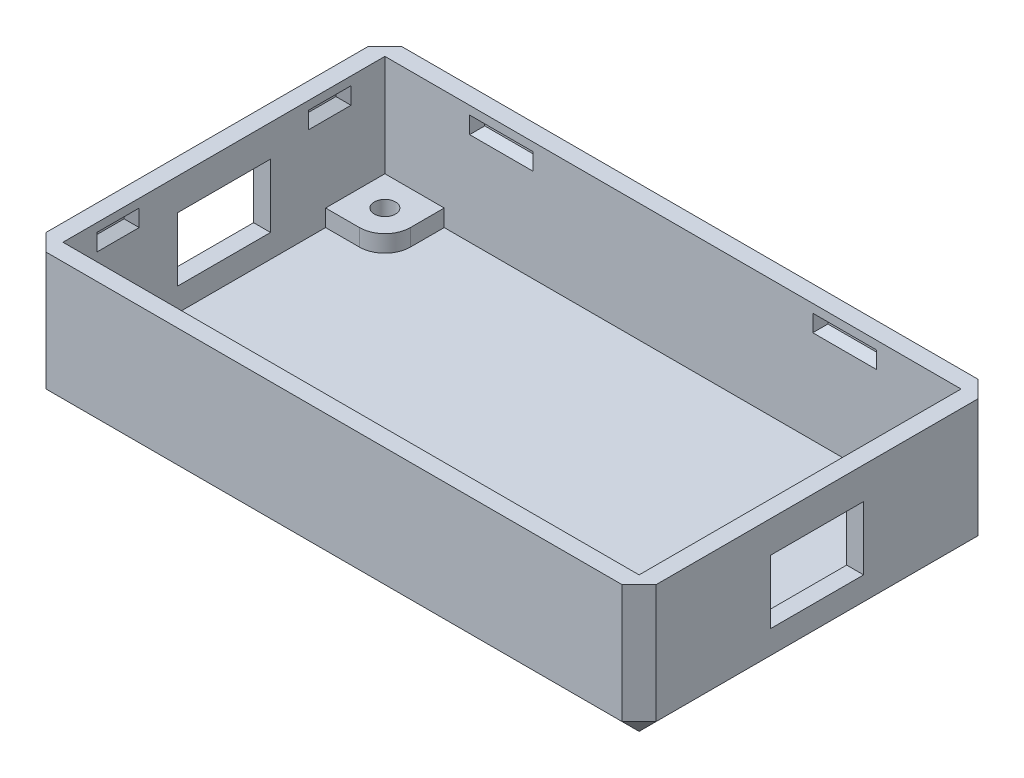
SolidWorks part; units mm, degrees
ref_plane "Front" through (0, 0, 0) normal (0, 0, 1) x (1, 0, 0)
ref_plane "Top" through (0, 0, 0) normal (0, 1, 0) x (1, 0, 0)
ref_plane "Right" through (0, 0, 0) normal (1, 0, 0) x (0, 0, -1)
sketch "Sketch1" plane through (0, 0, 0) normal (0, 1, 0) x (1, 0, 0)
  line L0 (-36, 21) -> (36, 21)
  line L1 (-34, -19) -> (34, -19)
  line L2 (-34, -19) -> (-34, 19)
  line L3 (-34, 19) -> (34, 19)
  line L4 (34, -19) -> (34, 19)
  line L5 (-34, -19) -> (34, 19) construction
  line L6 (-34, 19) -> (34, -19) construction
  line L7 (36, -21) -> (36, 21)
  line L8 (-36, -21) -> (36, -21)
  line L9 (-36, -21) -> (-36, 21)
  point P0 (0, 0)
  dimension "D1" = 38
  dimension "D2" = 68
  dimension "D3" = 2
extrude "Boss-Extrude1" add sketch "Sketch1" along normal blind 2 contours L1 L4 L3 L2 | L9 L8 L7 L0 L4 L1 L2 L3 region at (0, 0, -20.1665) region at (0, 0, 0)
extrude "Boss-Extrude2" add sketch "Sketch1<3>" along normal blind 14 from surface starting at face at (0, 2, 0)
sketch "Sketch1<3>" plane through (0, 0, 0) normal (0, 1, 0) x (1, 0, 0) same geometry as "Sketch1"
chamfer "Chamfer1" distance 2 angle 45 8 edges at (0, 0, 21) (36, 8, 21) (36, 0, 0) (36, 8, -21) (0, 0, -21) (-36, 8, -21) (-36, 0, 0) (-36, 8, 21)
sketch "Sketch2" plane through (0, 2, 0) normal (0, 1, 0) x (1, 0, 0)
  line L0 (-34, 12) -> (-30, 12)
  line L1 (-34, 19) -> (-27, 19)
  line L2 (-34, 19) -> (-34, 12)
  line L3 (-34, 12) -> (-27, 12) construction
  line L4 (-27, 19) -> (-27, 12) construction
  line L5 (-27, 19) -> (-27, 15)
  line L7 (-30.5, -15.5) -> (30.5, -15.5) construction
  line L8 (-30.5, -15.5) -> (-30.5, 15.5) construction
  line L9 (-30.5, 15.5) -> (30.5, 15.5) construction
  line L10 (30.5, -15.5) -> (30.5, 15.5) construction
  line L11 (-30.5, -15.5) -> (30.5, 15.5) construction
  line L12 (-30.5, 15.5) -> (30.5, -15.5) construction
  circle A0 centre (-30.5, 15.5) radius 1.25
  arc A1 (-30, 12) -> (-27, 15) centre (-30, 15) ccw
  point P7 (0, 0)
  point P8 (-27, 15.5)
  point P10 (-30.5, 12)
  point P13 (-27, 12)
  dimension "D1" = 3
  dimension "D3" = 2.5
  dimension "D2" = 31
extrude "Boss-Extrude3" add sketch "Sketch2" along normal blind 2
mirror "Mirror1" about plane through (0, 0, 0) normal (0, 0, 1) of "Boss-Extrude3"
mirror "Mirror2" about plane through (0, 0, 0) normal (1, 0, 0) of "Boss-Extrude3", "Mirror1"
sketch "Sketch3" plane through (0, 0, 0) normal (0, -1, 0) x (1, 0, 0)
  line L0 (-31.799, 17.75) -> (-29.201, 17.75)
  line L1 (-29.201, 17.75) -> (-27.9019, 15.5)
  line L2 (-27.9019, 15.5) -> (-29.201, 13.25)
  line L3 (-29.201, 13.25) -> (-31.799, 13.25)
  line L4 (-31.799, 13.25) -> (-33.0981, 15.5)
  line L5 (-33.0981, 15.5) -> (-31.799, 17.75)
  circle A1 centre (-30.5, 15.5) radius 2.5981 construction
  dimension "D1" = 4.5
extrude "Cut-Extrude1" cut sketch "Sketch3" against normal blind 1.6
mirror "Mirror3" about plane through (0, 0, 0) normal (0, 0, 1) of "Cut-Extrude1"
mirror "Mirror4" about plane through (0, 0, 0) normal (1, 0, 0) of "Mirror3", "Cut-Extrude1"
sketch "Sketch4" plane through (0, 2, 0) normal (0, 1, 0) x (1, 0, 0)
  circle A0 centre (30.5, -15.5) radius 1.25
  circle A1 centre (30.5, 15.5) radius 1.25
  circle A2 centre (-30.5, 15.5) radius 1.25
  circle A3 centre (-30.5, -15.5) radius 1.25
  circle A4 centre (-30.5, -15.5) radius 1.25 construction
extrude "Cut-Extrude2" cut sketch "Sketch4" against normal through all both and the other way through all
sketch "Sketch5" plane through (0, 0, 19) normal (0, 0, -1) x (-1, 0, 0)
  line L0 (34, 16) -> (-34, 16) construction
  line L1 (-24, 15) -> (-16.5, 15)
  line L2 (-24, 15) -> (-24, 13)
  line L3 (-24, 13) -> (-16.5, 13)
  line L4 (-16.5, 15) -> (-16.5, 13)
  line L5 (-34, 16) -> (-34, 2) construction
  dimension "D1" = 2
  dimension "D2" = 1
  dimension "D3" = 7.5
  dimension "D4" = 10
extrude "Cut-Extrude3" cut sketch "Sketch5" against normal blind 1 draft 38
mirror "Mirror5" about plane through (0, 0, 0) normal (0, 0, 1) of "Cut-Extrude3"
mirror "Mirror8" about plane through (0, 0, 0) normal (1, 0, 0) of "Mirror5", "Cut-Extrude3"
sketch "Sketch6" plane through (-34, 0, 0) normal (1, 0, 0) x (0, 0, -1)
  line L0 (19, 16) -> (-19, 16) construction
  line L1 (-15, 15) -> (-10, 15)
  line L2 (-15, 15) -> (-15, 13)
  line L3 (-15, 13) -> (-10, 13)
  line L4 (-10, 15) -> (-10, 13)
  dimension "D1" = 2
  dimension "D2" = 5
  dimension "D3" = 1
  dimension "D4" = 10
extrude "Cut-Extrude4" cut sketch "Sketch6" against normal blind 1 draft 38
mirror "Mirror6" about plane through (0, 0, 0) normal (1, 0, 0) of "Cut-Extrude4"
mirror "Mirror7" about plane through (0, 0, 0) normal (0, 0, 1) of "Mirror6", "Cut-Extrude4"
sketch "Sketch7" plane through (36, 0, 0) normal (1, 0, 0) x (0, 0, -1)
  line L1 (-5.5, 12.25) -> (5.5, 12.25)
  line L2 (-5.5, 12.25) -> (-5.5, 4.75)
  line L3 (-5.5, 4.75) -> (5.5, 4.75)
  line L4 (5.5, 12.25) -> (5.5, 4.75)
  point P4 (0, 4.75)
  dimension "D1" = 11
  dimension "D2" = 7.5
  dimension "D3" = 0.75
extrude "Cut-Extrude5" cut sketch "Sketch7" against normal through all
